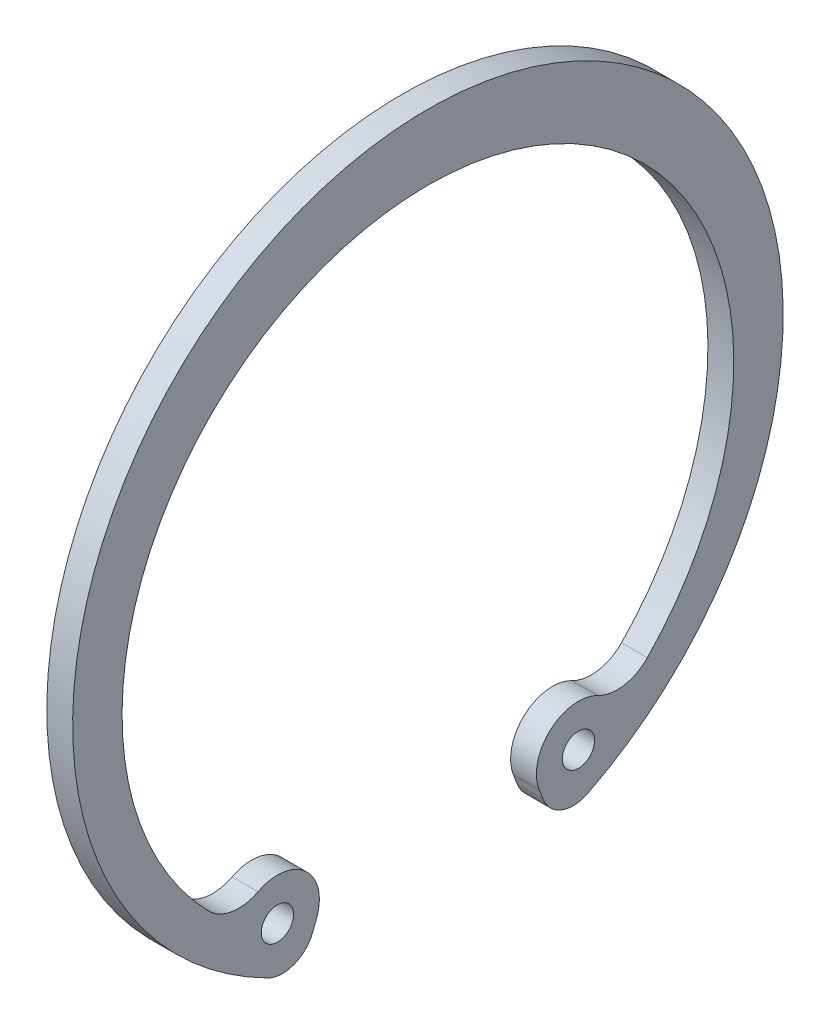
SolidWorks part; units mm, degrees
ref_plane "Plano frontal" through (0, 0, 0) normal (0, 0, 1) x (1, 0, 0)
ref_plane "Plano superior" through (0, 0, 0) normal (0, 1, 0) x (1, 0, 0)
ref_plane "Plano direito" through (0, 0, 0) normal (1, 0, 0) x (0, 0, -1)
ref_plane "Plane1" through (0, 0, 0) normal (1, 0, 0) x (0, 0, -1)
sketch "Sketch1" plane through (0, 0, 0) normal (1, 0, 0) x (0, 0, -1)
  line L0 (-8.9185, -23.2209) -> (-8.6161, -22.4335)
  line L1 (8.6161, -22.4335) -> (8.9185, -23.2209)
  arc A0 (12.3775, -24.557) -> (-12.3775, -24.557) centre (0, 0) ccw
  arc A1 (-12.3775, -24.557) -> (-8.9185, -23.2209) centre (-11.2523, -22.3246) ccw
  arc A2 (-8.6161, -22.4335) -> (-13.1517, -18.386) centre (-11.65, -21.2683) ccw
  arc A3 (-13.1517, -18.386) -> (-16.985, -17.7678) centre (-14.6534, -15.5038) cw
  arc A4 (-16.985, -17.7678) -> (16.985, -17.7678) centre (0, -1.275) cw
  arc A5 (16.985, -17.7678) -> (13.1517, -18.386) centre (14.6534, -15.5038) cw
  arc A6 (13.1517, -18.386) -> (8.6161, -22.4335) centre (11.65, -21.2683) ccw
  arc A7 (8.9185, -23.2209) -> (12.3775, -24.557) centre (11.2523, -22.3246) ccw
  circle A8 centre (11.65, -21.2683) radius 1.25
  circle A9 centre (-11.65, -21.2683) radius 1.25
extrude "Boss-Extrude1" add sketch "Sketch1" against normal blind 1 and the other way blind 1
